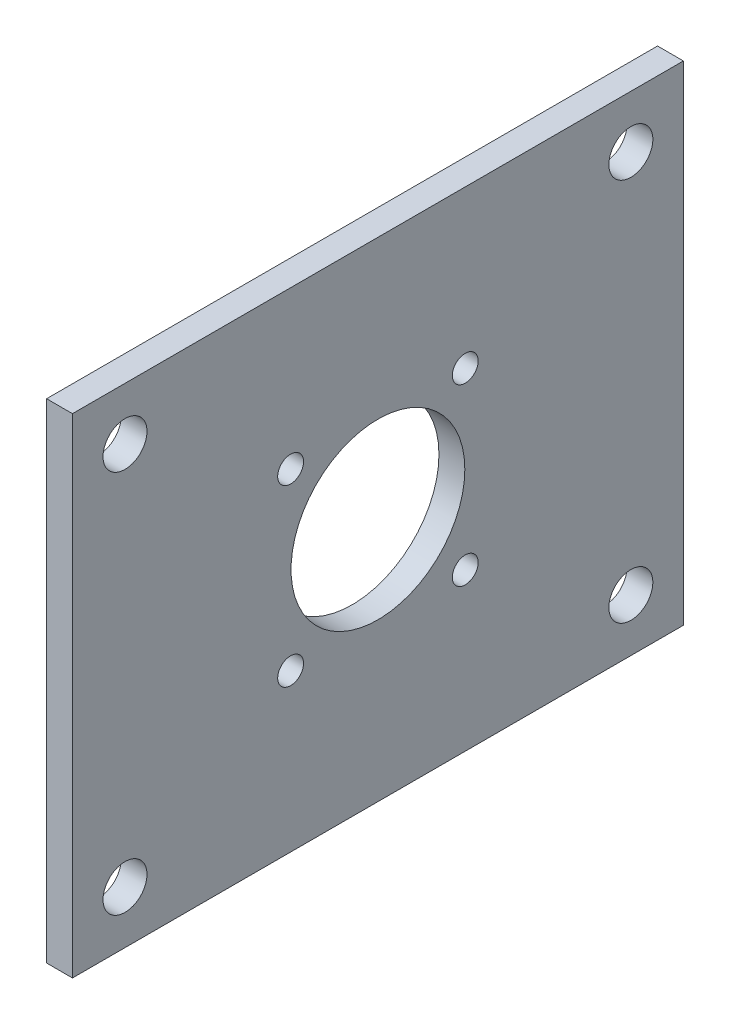
SolidWorks part; units mm, degrees
ref_plane "Front Plane" through (0, 0, 0) normal (0, 0, 1) x (1, 0, 0)
ref_plane "Top Plane" through (0, 0, 0) normal (0, 1, 0) x (1, 0, 0)
ref_plane "Right Plane" through (0, 0, 0) normal (1, 0, 0) x (0, 0, -1)
sketch "Sketch1" plane through (0, 0, 0) normal (1, 0, 0) x (0, 0, -1)
  line L1 (-37.5, -30) -> (37.5, -30)
  line L2 (-37.5, -30) -> (-37.5, 30)
  line L3 (-37.5, 30) -> (37.5, 30)
  line L4 (37.5, -30) -> (37.5, 30)
  line L5 (-37.5, -30) -> (37.5, 30) construction
  line L6 (-37.5, 30) -> (37.5, -30) construction
  point P0 (0, 0)
  dimension "D1" = 75
  dimension "D2" = 60
extrude "Boss-Extrude1" add sketch "Sketch1" along normal blind 1.5875 and the other way blind 1.5875
sketch "Sketch2" plane through (0, 0, 0) normal (1, 0, 0) x (0, 0, -1)
  line L0 (-37.5, 30) -> (-31.05, 30) construction
  line L1 (37.5, 30) -> (-37.5, 30) construction
  line L2 (-31.05, 30) -> (-31.05, 23.55) construction
  line L3 (0, 1.7463) -> (0, -1.7463) construction
  line L4 (1.7463, 0) -> (-1.7463, 0) construction
  circle A0 centre (-31.05, 23.55) radius 2.7
  circle A1 centre (31.05, 23.55) radius 2.7
  circle A2 centre (31.05, -23.55) radius 2.7
  circle A3 centre (-31.05, -23.55) radius 2.7
  dimension "D3" = 5.4
  dimension "D1" = 6.45
  dimension "D2" = 6.45
extrude "Cut-Extrude1" cut sketch "Sketch2" against normal through all both and the other way through all
sketch "Sketch3" plane through (0, 0, 0) normal (1, 0, 0) x (0, 0, -1)
  line L10 (-10.7188, 10.7188) -> (10.7188, 10.7188) construction
  line L11 (-10.7188, 10.7188) -> (-10.7188, -10.7188) construction
  line L12 (-10.7188, -10.7188) -> (10.7188, -10.7188) construction
  line L13 (10.7188, 10.7188) -> (10.7188, -10.7188) construction
  line L14 (-10.7188, 10.7188) -> (10.7188, -10.7188) construction
  line L15 (-10.7188, -10.7188) -> (10.7188, 10.7188) construction
  circle A13 centre (0, 0) radius 10.668
  circle A14 centre (-10.7188, 10.7188) radius 1.5875
  circle A15 centre (10.7188, 10.7188) radius 1.5875
  circle A16 centre (10.7188, -10.7188) radius 1.5875
  circle A17 centre (-10.7188, -10.7188) radius 1.5875
  point P5 (0, 0)
  dimension "D3" = 21.4376
  dimension "D5" = 3.175
  dimension "D6" = 3.175
  dimension "D1" = 21.336
  dimension "D4" = 3.175
  dimension "D7" = 3.175
  dimension "D2" = 21.4376
extrude "Cut-Extrude2" cut sketch "Sketch3" against normal through all both and the other way through all
